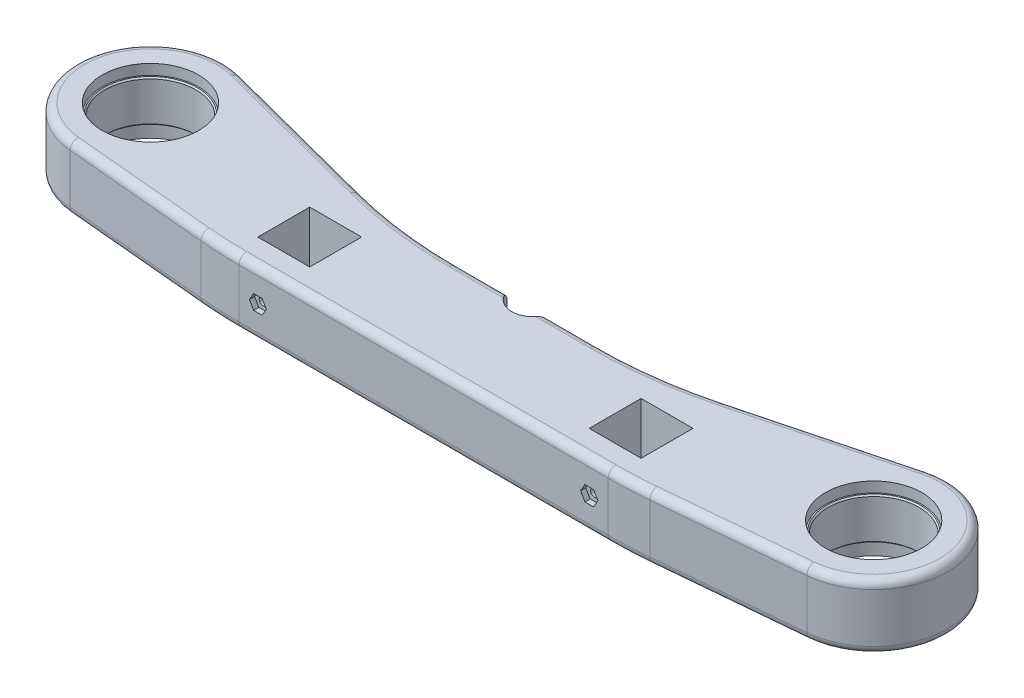
SolidWorks part; units mm, degrees
ref_plane "Front Plane" through (0, 0, 0) normal (0, 0, 1) x (1, 0, 0)
ref_plane "Top Plane" through (0, 0, 0) normal (0, 1, 0) x (1, 0, 0)
ref_plane "Right Plane" through (0, 0, 0) normal (1, 0, 0) x (0, 0, -1)
sketch "Sketch1" plane through (0, 0, 0) normal (0, 1, 0) x (1, 0, 0)
  line L0 (0, 0) -> (63.9, 0)
  line L1 (0, 0) -> (-63.9, 0)
  line L2 (-63.9, 0) -> (-139.4705, 0)
  line L3 (-53.9, 10) -> (-73.9, 10)
  line L4 (-53.9, 10) -> (-53.9, -10)
  line L5 (-53.9, -10) -> (-73.9, -10)
  line L6 (-73.9, 10) -> (-73.9, -10)
  line L7 (-53.9, 10) -> (-73.9, -10) construction
  line L8 (-53.9, -10) -> (-73.9, 10) construction
  line L9 (73.9, 10) -> (53.9, 10)
  line L10 (73.9, 10) -> (73.9, -10)
  line L11 (73.9, -10) -> (53.9, -10)
  line L12 (53.9, 10) -> (53.9, -10)
  line L13 (73.9, 10) -> (53.9, -10) construction
  line L14 (73.9, -10) -> (53.9, 10) construction
  line L15 (63.9, 0) -> (139.4705, 0)
  line L16 (-139.4705, 0) -> (-139.4705, 14.1291)
  line L17 (-48.9, -20) -> (-78.9, -20)
  line L18 (-48.9, -20) -> (-48.9, 20)
  line L19 (-48.9, 20) -> (-78.9, 20)
  line L20 (-78.9, -20) -> (-78.9, 20)
  line L21 (-48.9, -20) -> (-78.9, 20) construction
  line L22 (-48.9, 20) -> (-78.9, -20) construction
  line L23 (78.9, -20) -> (48.9, -20)
  line L24 (78.9, -20) -> (78.9, 20)
  line L25 (78.9, 20) -> (48.9, 20)
  line L26 (48.9, -20) -> (48.9, 20)
  line L27 (78.9, -20) -> (48.9, 20) construction
  line L28 (78.9, 20) -> (48.9, -20) construction
  line L29 (139.4705, 0) -> (139.4705, 14.1291)
  line L30 (78.9, -20) -> (142.0531, -14.2537)
  line L31 (-78.9, -20) -> (-142.0531, -14.2537)
  line L32 (0, 10) -> (0, 22.15)
  line L33 (-48.9, 20) -> (-132.2902, 41.7097)
  line L34 (-63.9, -20) -> (63.9, -20)
  line L35 (-48.9, 20) -> (-7.8094, 20)
  line L36 (48.9, 20) -> (7.8094, 20)
  line L37 (48.9, 20) -> (133.6344, 42.0597)
  line L38 (-63.9, 10) -> (63.9, 10)
  line L39 (63.9, 10) -> (0, 10)
  circle A6 centre (0, 22.15) radius 8.1
  circle A7 centre (-139.4705, 14.1291) radius 28.5
  circle A8 centre (139.4705, 14.1291) radius 28.5
  circle A9 centre (-139.4705, 14.1291) radius 18.6
  circle A10 centre (139.4705, 14.1291) radius 18.6
  dimension "D1" = 20
  dimension "D9" = 30
  dimension "D13" = 14.1291
  dimension "D15" = 57
  dimension "D16" = 57
  dimension "D17" = 37.2
  dimension "D18" = 37.2
  dimension "D2" = 20
  dimension "D3" = 20
  dimension "D4" = 20
  dimension "D5" = 63.9
  dimension "D6" = 63.9
  dimension "D7" = 75.5705
  dimension "D8" = 75.5705
  dimension "D10" = 40
  dimension "D11" = 40
  dimension "D12" = 30
  dimension "D14" = 14.1291
extrude "Boss-Extrude1" add sketch "Sketch1" along normal blind 25 contours A9 A7 | A7 L31 L20 L2 | A7 L2 L20 L19 L33 | L20 L17 L18 L1 L4 L5 L6 L2 | L3 L38 L18 L19 L20 L2 L6 | L38 L4 L1 L18 | L38 L18 L1 L0 L26 | A6 L35 L18 L38 L32 | L18 L34 L26 L0 L1 | A6 L32 L38 L26 L36 | L26 L38 L9 L10 L15 L24 L25 | L26 L23 L24 L15 L10 L11 L12 L0 | L38 L26 L0 L12 | A8 L37 L25 L24 L15 | A8 L15 L24 L30 | A10 A8 region at (0, 0, -5) region at (0, 0, 10) region at (51.4, 0, -5) region at (63.9, 0, 12.5) region at (-63.9, 0, 12.5) region at (-51.4, 0, -5) region at (26.0575, 0, -14.8094) region at (65.6857, 0, -13.5714) region at (-65.6857, 0, -13.5714) region at (-26.0575, 0, -14.8094) region at (94.8448, 0, -17.7504) region at (-94.8448, 0, -17.7504) region at (100.5025, 0, 9.589) region at (156.4075, 0, -36.04) region at (-100.5025, 0, 9.589) region at (-117.5596, 0, -31.0661)
fillet "Fillet1" radius 170 2 edges at (78.9, 12.5, 20) (-78.9, 12.5, 20)
fillet "Fillet2" radius 170 2 edges at (48.9, 12.5, -20) (-48.9, 12.5, -20)
fillet "Fillet3" radius 3 26 edges at (-17.4717, 0, -20) (-48.7238, 0, -21.3765) (17.4717, 0, -20) (48.7238, 0, -21.3765) (101.1271, 0, -33.5967) (167.5465, 0, -19.0269) (114.3198, 0, 16.7772) (78.8921, 0, 19.8251) (0, 0, 20) (-78.8921, 0, 19.8251) (-114.3198, 0, 16.7772) (-167.5465, 0, -19.0269) (-17.4717, 25, -20) (-48.7238, 25, -21.3765) (17.4717, 25, -20) (48.7238, 25, -21.3765) (101.1271, 25, -33.5967) (167.5465, 25, -19.0269) (114.3198, 25, 16.7772) (78.8921, 25, 19.8251) (0, 25, 20) (-78.8921, 25, 19.8251) (-114.3198, 25, 16.7772) (-167.5465, 25, -19.0269) (-101.1271, 0, -33.5967) (-101.1271, 25, -33.5967)
sketch "Sketch2" plane through (0, 25, 0) normal (0, 1, 0) x (1, 0, 0)
  circle A0 centre (-139.4705, 14.1291) radius 17.6
  circle A1 centre (139.4705, 14.1291) radius 17.6
  circle A2 centre (139.4705, 14.1291) radius 18.6 construction
  circle A3 centre (-139.4705, 14.1291) radius 18.6 construction
  circle A4 centre (139.4705, 14.1291) radius 18.6
  circle A5 centre (-139.4705, 14.1291) radius 18.6
extrude "Boss-Extrude2" add sketch "Sketch2" against normal blind 16 from offset 4 offset against normal yes
chamfer "Chamfer1" distance 0.5 angle 45 4 edges at (139.4705, 5, 3.4709) (139.4705, 21, 3.4709) (-139.4705, 21, 3.4709) (-139.4705, 5, 3.4709)
sketch "Sketch3" plane through (0, 0, 10) normal (0, 0, -1) x (-1, 0, 0)
  line L0 (-73.9, 12.5) -> (-53.9, 12.5)
  line L1 (-73.9, 25) -> (-73.9, 0) construction
  line L2 (-53.9, 25) -> (-53.9, 0) construction
  line L3 (53.9, 12.5) -> (73.9, 12.5)
  line L4 (53.9, 25) -> (53.9, 0) construction
  line L5 (73.9, 25) -> (73.9, 0) construction
  circle A0 centre (-63.9, 12.5) radius 1.48
  circle A1 centre (63.9, 12.5) radius 1.48
extrude "Cut-Extrude1" cut sketch "Sketch3" against normal blind 16 and the other way blind 96 contours L3 A1 | L3 A1 | L0 A0 | L0 A0 region at (63.9, 13.1281, 10) region at (63.9, 11.8719, 10) region at (-63.9, 13.1281, 10) region at (-63.9, 11.8719, 10)
sketch "Sketch4" plane through (0, 0, -10) normal (0, 0, 1) x (1, 0, 0)
  circle A0 centre (-63.9, 12.5) radius 2.9
  circle A1 centre (63.9, 12.5) radius 2.9
extrude "Cut-Extrude2" cut sketch "Sketch4" against normal blind 46 from offset 8.5 offset against normal yes
sketch "Sketch5" plane through (0, 0, 10) normal (0, 0, -1) x (-1, 0, 0)
  line L1 (-67.25, 12.5) -> (-65.575, 9.5988)
  line L2 (-65.575, 9.5988) -> (-62.225, 9.5988)
  line L3 (-62.225, 9.5988) -> (-60.55, 12.5)
  line L4 (-60.55, 12.5) -> (-62.225, 15.4012)
  line L5 (-62.225, 15.4012) -> (-65.575, 15.4012)
  line L6 (-65.575, 15.4012) -> (-67.25, 12.5)
  line L7 (60.65, 12.5) -> (62.275, 9.6854)
  line L8 (62.275, 9.6854) -> (65.525, 9.6854)
  line L9 (65.525, 9.6854) -> (67.15, 12.5)
  line L10 (67.15, 12.5) -> (65.525, 15.3146)
  line L11 (65.525, 15.3146) -> (62.275, 15.3146)
  line L12 (62.275, 15.3146) -> (60.65, 12.5)
  circle A0 centre (-63.9, 12.5) radius 3.35
  circle A1 centre (-63.9, 12.5) radius 2.9012 construction
  circle A2 centre (63.9, 12.5) radius 3.25
  circle A3 centre (63.9, 12.5) radius 2.8146 construction
  circle M1 centre (63.9, 12.5) radius 1.48
extrude "Cut-Extrude3" cut sketch "Sketch5" against normal blind 46 from offset 8 contours L11 L12 L7 L8 L9 L10 M1 | L5 L6 L1 L2 L3 L4 region at (63.9, 12.5, 10) region at (-61.537, 13.8643, 10) offset against normal yes
